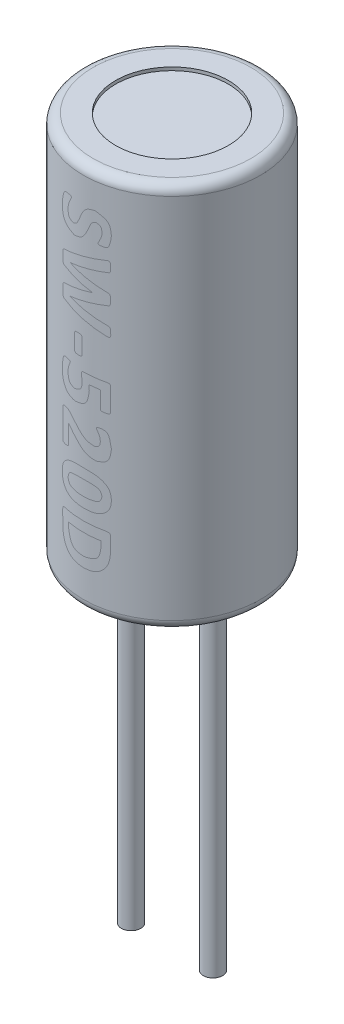
SolidWorks part; units mm, degrees
material "6061-T6 (SS)"
ref_plane "Front Plane" through (0, 0, 0) normal (0, 0, 1) x (1, 0, 0)
ref_plane "Top Plane" through (0, 0, 0) normal (0, 1, 0) x (1, 0, 0)
ref_plane "Right Plane" through (0, 0, 0) normal (1, 0, 0) x (0, 0, -1)
sketch "Sketch1" plane through (0, 0, 0) normal (0, 0, 1) x (1, 0, 0)
  line L1 (0, 0) -> (2.75, 0)
  line L2 (0, 0) -> (0, 12)
  line L3 (0, 12) -> (2.75, 12)
  line L4 (2.75, 0) -> (2.75, 12)
  dimension "D1" = 2.75
  dimension "D2" = 12
revolve "Revolve1" add sketch "Sketch1" angle 360 about L2
sketch "Sketch2" plane through (0, 12, 0) normal (0, 1, 0) x (1, 0, 0)
  circle A0 centre (0, 0) radius 1.75
  dimension "D1" = 3.5
extrude "Cut-Extrude1" cut sketch "Sketch2" against normal blind 0.1
sketch "Sketch3" plane through (0, 0, 0) normal (0, -1, 0) x (1, 0, 0)
  circle A0 centre (0, 0) radius 1.75
  dimension "D1" = 3.5
extrude "Cut-Extrude2" cut sketch "Sketch3" against normal blind 0.1
fillet "Fillet1" radius 0.3 2 edges at (0, 0, -2.75) (0, 12, -2.75)
sketch "Sketch4" plane through (0, 0.1, 0) normal (0, -1, 0) x (1, 0, 0)
  line L0 (-1.27, 0) -> (1.27, 0) construction
  circle A0 centre (1.27, 0) radius 0.3
  circle A1 centre (-1.27, 0) radius 0.3
  dimension "D2" = 0.6
  dimension "D1" = 2.54
extrude "Boss-Extrude1" add sketch "Sketch4" along normal blind 10.5
sketch "Sketch5" plane through (0, 0, 0) normal (0, 0, 1) x (1, 0, 0)
  line L0 (0, 0) -> (0, 0.5) construction
  line L1 (0, 0.5) -> (0, 11.5)
  line L2 (0, 11.5) -> (0, 12) construction
  line L3 (1.75, 12) -> (-1.75, 12) construction
  line L4 (0, 11.5) -> (2.5, 11.5)
  line L5 (2.5, 11.5) -> (2.5, 0.5)
  line L6 (2.5, 0.5) -> (0, 0.5)
  dimension "D1" = 2.5
  dimension "D2" = 0.5
  dimension "D3" = 0.5
revolve "Cut-Revolve1" cut sketch "Sketch5" angle 360 about L1
ref_plane "Plane1" through (0, 0, 3) normal (0, 0, 1) x (1, 0, 0)
sketch "Sketch6" plane through (0, 0, 3) normal (0, 0, 1) x (1, 0, 0)
  line L0 (0, 0) -> (0, 1) construction
  line L1 (0, 1) -> (-0.75, 1) construction
  line L2 (-0.75, 1) -> (-0.75, 11) construction
  line L3 (0, 1) -> (0.75, 1) construction
  line L4 (0.75, 1) -> (0.75, 11) construction
  line L5 (0.75, 11) -> (-0.75, 11) construction
  text T0 "SW-520D" font "Calibri" height 1.5
  point P6 (-0.6001, 11)
  dimension "D1" = 0.75
  dimension "D2" = 1
  dimension "D3" = 10
wrap "Wrap1" sketch "Sketch6" wrap type scribe source sketch "Sketch6"
